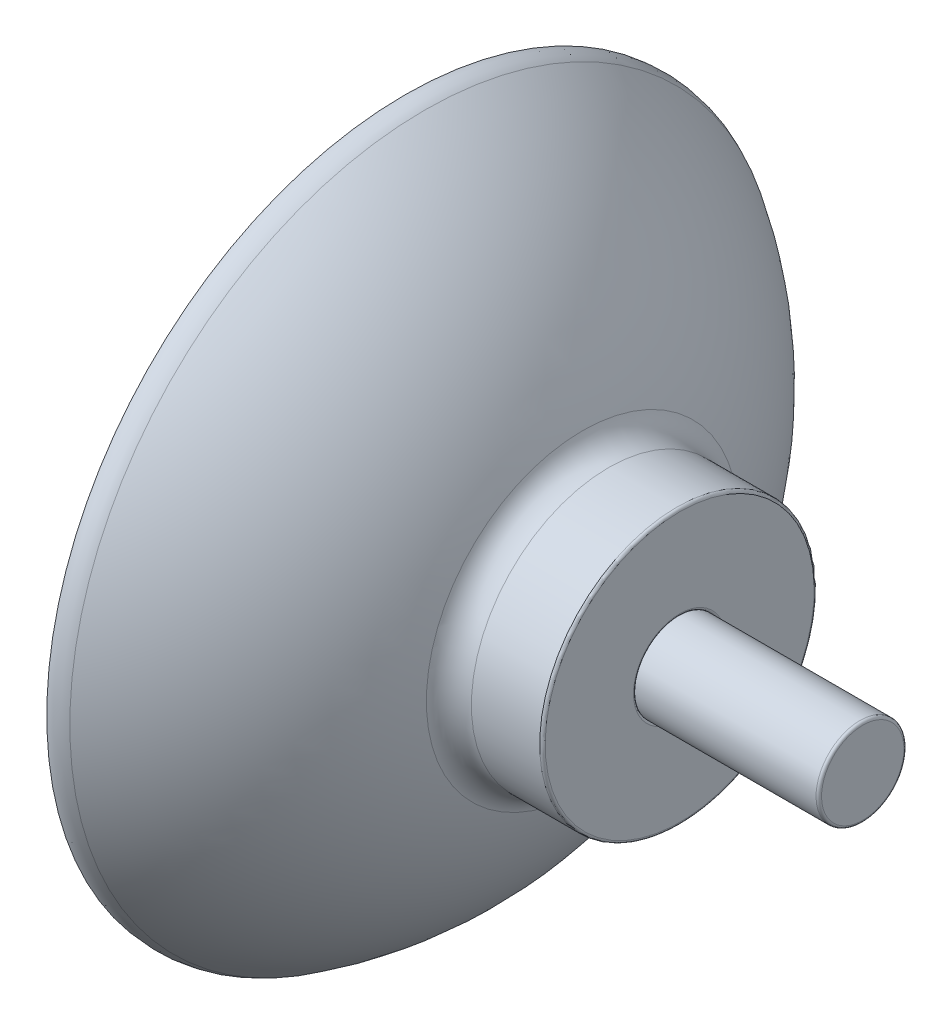
SolidWorks part; units mm, degrees
ref_plane "前视基准面" through (0, 0, 0) normal (0, 0, 1) x (1, 0, 0)
ref_plane "上视基准面" through (0, 0, 0) normal (0, 1, 0) x (1, 0, 0)
ref_plane "右视基准面" through (0, 0, 0) normal (1, 0, 0) x (0, 0, -1)
sketch "草图1" plane through (0, 0, 0) normal (0, 0, 1) x (1, 0, 0)
  line L0 (0, 0) -> (-10, 0) construction
  line L1 (0, 0) -> (5, 0) construction
  line L2 (0, 0) -> (0, 7.5)
  line L3 (0, 7.5) -> (5, 7.5)
  line L4 (5, 0) -> (5, 7.5)
  line L9 (2, 0) -> (4, 0) construction
  line L10 (2, 0) -> (2, 4.75)
  line L11 (2, 4.75) -> (4, 4.75)
  line L12 (4, 0) -> (4, 4.75)
  line L13 (-10, 0) -> (-10, 20) construction
  line L14 (-10, 20) -> (-10, 19.5)
  line L15 (5, 0) -> (4, 0)
  line L16 (2, 0) -> (0, 0)
  line L17 (4, 2.375) -> (5, 2.375)
  arc A0 (0, 7.5) -> (-10, 20) centre (-19.3122, 2.3002) ccw
  arc A1 (-10, 19.5) -> (0, 4) centre (-21.7836, 0.9219) cw
  dimension "D8" = 20
  dimension "D11" = 22
  dimension "D1" = 5
  dimension "D2" = 7.5
  dimension "D3" = 1
  dimension "D4" = 2
  dimension "D5" = 4.75
  dimension "D6" = 20
  dimension "D7" = 10
  dimension "D9" = 0.5
  dimension "D10" = 3.5
revolve "旋转1" add sketch "草图1" angle 360 about L0 region at (0.0901, 2, 0) region at (-3.1385, 12.951, 0)
fillet "圆角1" radius 0.15 5 edges at (4, 2.375, 0) (5, 2.375, 0) (5, 7.5, 0) (-10, 19.5, 0) (0, 4, 0)
fillet "圆角2" radius 1.5 2 edges at (0, 7.5, 0) (-10, 20, 0)
sketch "草图2" plane through (0, 0, 0) normal (0, 0, 1) x (1, 0, 0)
  line L0 (2, 0) -> (2, 4.75)
  line L1 (2, -4.75) -> (2, 4.75) construction
  line L2 (2, 4.75) -> (4, 4.75)
  line L3 (4, 4.75) -> (4, -4.75) construction
  line L4 (4, 4.75) -> (4, 2.4)
  line L5 (4, 2.4) -> (15, 2.4)
  line L6 (15, 2.4) -> (15, 0)
  line L7 (15, 0) -> (2, 0)
  line L8 (5, -2.525) -> (5, 2.525) construction
  dimension "D1" = 10
  dimension "D2" = 2.35
  dimension "D3" = 2.4
revolve "旋转2" add sketch "草图2" angle 360 about L7
fillet "圆角3" radius 0.15 1 edges at (15, 2.4, 0)
